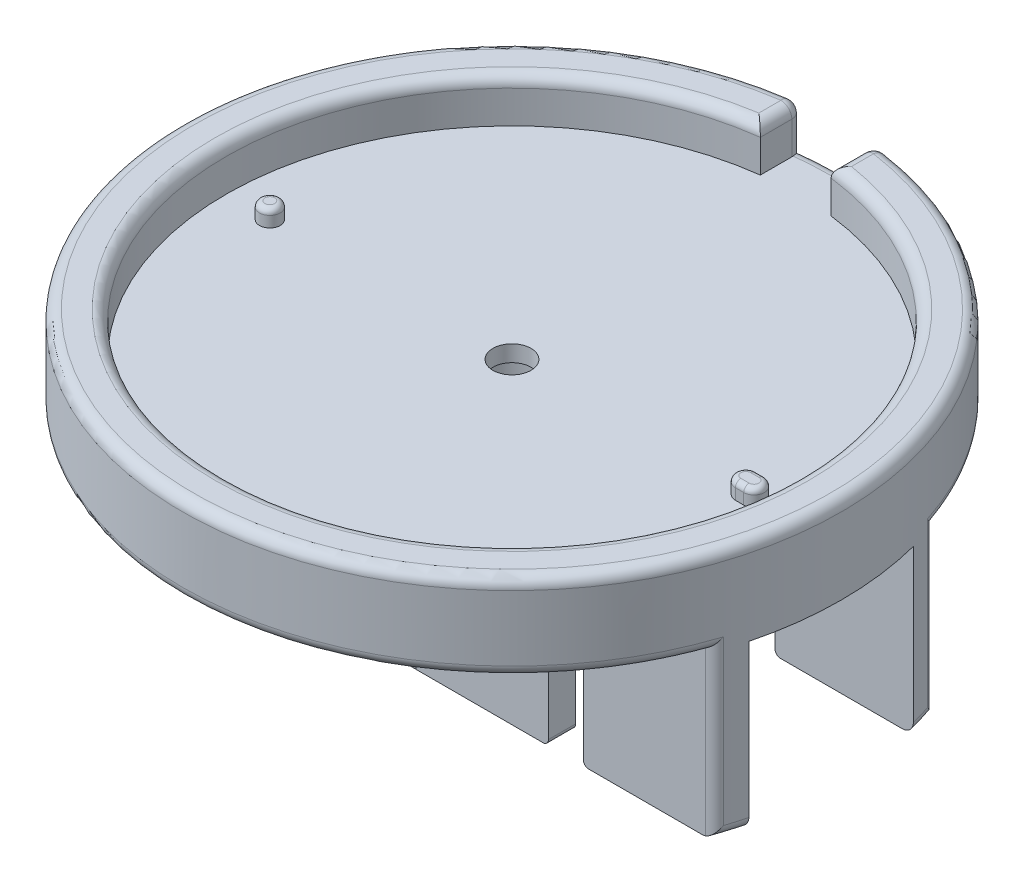
SolidWorks part; units mm, degrees
ref_plane "정면" through (0, 0, 0) normal (0, 0, 1) x (1, 0, 0)
ref_plane "윗면" through (0, 0, 0) normal (0, 1, 0) x (1, 0, 0)
ref_plane "우측면" through (0, 0, 0) normal (1, 0, 0) x (0, 0, -1)
sketch "스케치1" plane through (0, 0, 0) normal (0, 1, 0) x (1, 0, 0)
  circle A0 centre (0, 0) radius 60.5
  circle A1 centre (0, 0) radius 3.5
  dimension "D1" = 121
  dimension "D2" = 7
extrude "보스-돌출1" add sketch "스케치1" along normal blind 8
sketch "스케치2" plane through (0, 8, 0) normal (0, 1, 0) x (1, 0, 0)
  line L0 (0, 0) -> (0, 60) construction
  line L1 (6.5, 60.1498) -> (6.5, 52.0961)
  line L2 (-6.5, 60.1498) -> (-6.5, 52.0961)
  arc A0 (-6.5, 52.0961) -> (6.5, 52.0961) centre (0, 0) ccw
  circle A1 centre (0, 0) radius 60.5
  arc A2 (-6.5, 60.1498) -> (6.5, 60.1498) centre (0, 0) ccw
  circle A4 centre (0, 0) radius 60.5 construction
  circle A5 centre (0, 0) radius 52.5 construction
  point P4 (52, 0)
  point P10 (57.3783, 17.5423)
  dimension "D3" = 6.5
  dimension "D4" = 6.5
  dimension "D1" = 0
  dimension "D2" = 8
extrude "보스-돌출2" add sketch "스케치2" along normal blind 8
sketch "스케치3" plane through (0, 8, 0) normal (0, 1, 0) x (1, 0, 0)
  line L0 (-52.5, 0) -> (52.5, 0) construction
  line L1 (42.93, 0) -> (44.45, 0) construction
  line L2 (42.93, 1.9) -> (44.45, 1.9)
  line L3 (42.93, -1.9) -> (44.45, -1.9)
  arc A0 (-6.5, 52.0961) -> (6.5, 52.0961) centre (0, 0) ccw construction
  arc A1 (-6.5, 52.0961) -> (6.5, 52.0961) centre (0, 0) ccw construction
  arc A2 (42.93, 1.9) -> (42.93, -1.9) centre (42.93, 0) ccw
  arc A3 (44.45, -1.9) -> (44.45, 1.9) centre (44.45, 0) ccw
  circle A4 centre (-44.45, 0) radius 1.9
  point P11 (43.69, 0)
  dimension "D3" = 1.9
  dimension "D4" = 3.8
  dimension "D1" = 43.69
  dimension "D2" = 1.52
  dimension "D5" = 44.45
extrude "보스-돌출3" add sketch "스케치3" along normal blind 3
sketch "스케치4" plane through (0, 0, 0) normal (0, -1, 0) x (1, 0, 0)
  line L0 (-60.5, 0) -> (60.5, 0) construction
  line L1 (-58.5853, 15.1) -> (58.5853, 15.1)
  line L2 (-58.5853, -15.1) -> (58.5853, -15.1)
  line L3 (-57.0635, 20.1) -> (57.0635, 20.1)
  line L4 (-57.0635, -20.1) -> (57.0635, -20.1)
  circle A0 centre (0, 0) radius 60.5 construction
  arc A1 (-57.0635, 20.1) -> (-58.5853, 15.1) centre (0, 0) ccw
  arc A2 (-58.5853, -15.1) -> (-57.0635, -20.1) centre (0, 0) ccw
  arc A3 (58.5853, 15.1) -> (57.0635, 20.1) centre (0, 0) ccw
  arc A4 (57.0635, -20.1) -> (58.5853, -15.1) centre (0, 0) ccw
  dimension "D1" = 15.1
  dimension "D2" = 15.1
  dimension "D3" = 5
  dimension "D4" = 5
extrude "보스-돌출4" add sketch "스케치4" along normal blind 30
sketch "스케치7" plane through (0, 0, 0) normal (1, 0, 0) x (0, 0, -1)
  line L0 (-20.1, -30) -> (-50.1, 0)
  line L1 (-60.5, 0) -> (-20.1, 0) construction
  line L2 (-20.1, -30) -> (-20.1, 0) construction
  dimension "D1" = 45
rib "보강대2" sketch "스케치7" sketch "스케치7" thickness 5 extrusion direction parallel to sketch draft on no parameters "D1"=5
mirror "대칭 복사1" about plane through (0, 0, 0) normal (0, 0, 1) of "보강대2"
sketch "스케치8" plane through (0, 0, 20.1) normal (0, 0, 1) x (1, 0, 0)
  line L0 (-57.0635, -15) -> (57.0635, -15) construction
  line L1 (-57.0635, -30) -> (-57.0635, 0) construction
  line L2 (57.0635, -30) -> (57.0635, 0) construction
  circle A0 centre (-30, -15) radius 3.2
  circle A1 centre (30, -15) radius 3.2
  point P12 (0, -15)
  dimension "D1" = 6.4
  dimension "D2" = 30
  dimension "D3" = 30
extrude "컷-돌출1" cut sketch "스케치8" against normal through all
fillet "필렛1" radius 2 17 edges at (57.0635, -15, 20.1) (-57.0635, -15, 20.1) (-57.8784, -30, 17.6164) (57.8784, -30, 17.6164) (-57.8784, -30, -17.6164) (57.8784, -30, -17.6164) (57.0635, -15, -20.1) (-57.0635, -15, -20.1) (0, 0, -60.5) (0, 0, 60.5) (0, 16, 60.5) (6.5, 12, -60.1498) (0, 8, -60.5) (-6.5, 12, -60.1498) (6.5, 16, -56.1229) (-6.5, 16, -56.1229) (0, 16, 52.5)
fillet "필렛4" radius 1 5 edges at (43.69, 11, -1.9) (46.35, 11, 0) (43.69, 11, 1.9) (41.03, 11, 0) (-44.45, 11, 1.9)
sketch "스케치9" plane through (0, 0, 20.1) normal (0, 0, 1) x (1, 0, 0)
  line L0 (-26.8, -15) -> (-26.8, -30)
  line L1 (-2.5, -30) -> (-54.9385, -30) construction
  line L2 (-26.8, -30) -> (-33.2, -30)
  line L3 (-33.2, -30) -> (-33.2, -15)
  line L4 (0, 0) -> (0, -30) construction
  line L5 (2.5, -30) -> (-2.5, -30) construction
  line L6 (33.2, -30) -> (33.2, -15)
  line L7 (26.8, -30) -> (33.2, -30)
  line L8 (26.8, -15) -> (26.8, -30)
  circle A0 centre (-30, -15) radius 3.2 construction
  arc A1 (-33.2, -15) -> (-26.8, -15) centre (-30, -15) ccw
  arc A2 (33.2, -15) -> (26.8, -15) centre (30, -15) cw
extrude "컷-돌출2" cut sketch "스케치9" against normal through all
fillet "필렛5" radius 1 8 edges at (-33.2, -30, 17.6) (-26.8, -30, 17.6) (26.8, -30, 17.6) (33.2, -30, 17.6) (-33.2, -30, -17.6) (-26.8, -30, -17.6) (26.8, -30, -17.6) (33.2, -30, -17.6)
sketch "스케치10" plane through (0, 0, 0) normal (0, -1, 0) x (1, 0, 0)
  circle A1 centre (0, 0) radius 3.5 construction
  circle A2 centre (0, 0) radius 6.5
  circle A3 centre (0, 0) radius 6.5
  circle A4 centre (0, 0) radius 3.5
  dimension "D1" = 3
extrude "컷-돌출3" cut sketch "스케치10" against normal blind 5
